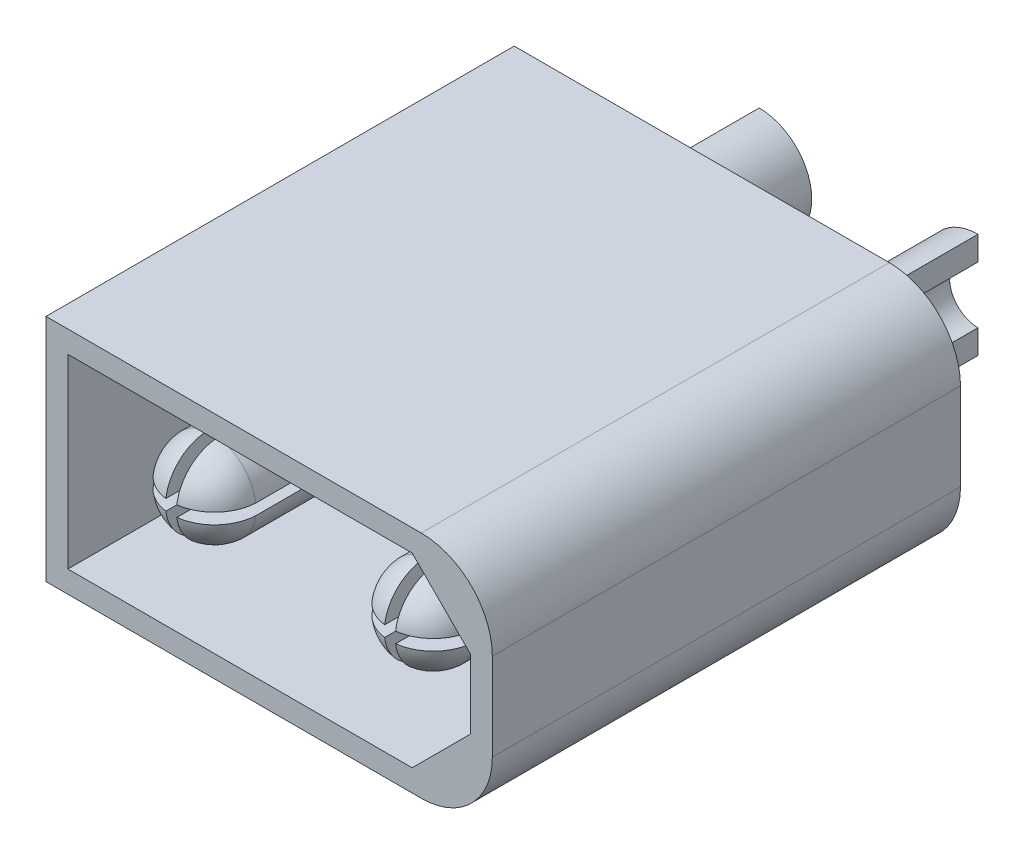
SolidWorks part; units mm, degrees
ref_plane "Front Plane" through (0, 0, 0) normal (0, 0, 1) x (1, 0, 0)
ref_plane "Top Plane" through (0, 0, 0) normal (0, 1, 0) x (1, 0, 0)
ref_plane "Right Plane" through (0, 0, 0) normal (1, 0, 0) x (0, 0, -1)
sketch "Sketch1" plane through (0, 0, 0) normal (0, 0, 1) x (1, 0, 0)
  line L0 (0, 0) -> (10.2, 0) construction
  line L1 (0, -2.625) -> (0, 2.625)
  line L2 (0, 2.625) -> (8.575, 2.625)
  line L4 (10.2, 1) -> (10.2, -1)
  line L5 (5.1, 0) -> (5.1, 1.3562) construction
  line L7 (0, -2.625) -> (8.575, -2.625)
  line L8 (0.5, 2.125) -> (8.3679, 2.125)
  line L9 (8.3679, 2.125) -> (9.7, 0.7929)
  line L10 (9.7, 0.7929) -> (9.7, -0.7929)
  line L11 (8.3679, -2.125) -> (9.7, -0.7929)
  line L12 (0.5, -2.125) -> (8.3679, -2.125)
  line L13 (0.5, -2.125) -> (0.5, 2.125)
  line L14 (8.575, 2.625) -> (10.2, 1) construction
  line L15 (8.575, -2.625) -> (10.2, -1) construction
  circle A0 centre (2.6, 0) radius 1
  circle A2 centre (7.6, 0) radius 1
  arc A3 (8.575, 2.625) -> (10.2, 1) centre (8.575, 1) cw
  arc A4 (8.575, -2.625) -> (10.2, -1) centre (8.575, -1) ccw
  dimension "D6" = 2
  dimension "D1" = 5.25
  dimension "D2" = 10.2
  dimension "D3" = 135
  dimension "D4" = 2.5
  dimension "D7" = 2
  dimension "D5" = 0.5
extrude "Boss-Extrude1" add sketch "Sketch1" along normal blind 10.7 contours L1 L7 A4 L4 A3 L2 L12 L13 L8 L9 L10 L11 region at (0.1147, 0, 0)
extrude "Boss-Extrude5" add sketch "Sketch1<4>" along normal blind 9.5 separate body contours A0 | A2 region at (2.6, 0, 0)
sketch "Sketch1<4>" plane through (0, 0, 0) normal (0, 0, 1) x (1, 0, 0) same geometry as "Sketch1"
ref_plane "Plane1" through (0, 0, 1) normal (0, 0, -1) x (-1, 0, 0)
sketch "Sketch3" plane through (0, 0, 1) normal (0, 0, -1) x (-1, 0, 0)
  line L0 (-0.5, -2.125) -> (-0.5, 2.125) construction
  line L1 (-0.5, -2.125) -> (-8.3679, -2.125) construction
  line L2 (-8.3679, -2.125) -> (-9.7, -0.7929) construction
  line L3 (-9.7, 0.7929) -> (-9.7, -0.7929) construction
  line L4 (-8.3679, 2.125) -> (-9.7, 0.7929) construction
  line L5 (-0.5, 2.125) -> (-8.3679, 2.125) construction
  line L6 (-0.5, -2.125) -> (-0.5, 2.125)
  line L7 (-0.5, -2.125) -> (-8.3679, -2.125)
  line L8 (-8.3679, -2.125) -> (-9.7, -0.7929)
  line L9 (-9.7, 0.7929) -> (-9.7, -0.7929)
  line L10 (-8.3679, 2.125) -> (-9.7, 0.7929)
  line L11 (-0.5, 2.125) -> (-8.3679, 2.125)
extrude "Boss-Extrude3" add sketch "Sketch3" against normal blind 2.5
dome "Dome1" faces to dome 1 distance 0.95 reverse direction no elliptical dome no face at (6.6, 0, 9.5) parameters "D1"=0.95
dome "Dome2" faces to dome 1 distance 0.95 reverse direction no elliptical dome no face at (3.6, 0, 9.5) parameters "D1"=0.95
ref_plane "Plane2" through (0, 0, 6) normal (0, 0, 1) x (1, 0, 0)
sketch "Sketch4" plane through (0, 0, 6) normal (0, 0, 1) x (1, 0, 0)
  line L0 (7.6, 0) -> (2.6, 0) construction
  line L1 (5.1, 0) -> (5.1, -4.8964) construction
  line L2 (7.6, 0) -> (7.6, 1) construction
  line L3 (7.475, 0.9922) -> (7.475, 0.125)
  line L4 (7.725, 0.9922) -> (7.725, 0.125)
  line L5 (8.5922, -0.125) -> (7.725, -0.125)
  line L6 (8.5922, 0.125) -> (7.725, 0.125)
  line L7 (7.475, -0.9922) -> (7.475, -0.125)
  line L8 (7.725, -0.9922) -> (7.725, -0.125)
  line L9 (6.6078, 0.125) -> (7.475, 0.125)
  line L10 (6.6078, -0.125) -> (7.475, -0.125)
  line L11 (2.6, 0) -> (2.6, 1) construction
  line L12 (3.5922, -0.125) -> (2.725, -0.125)
  line L13 (3.5922, 0.125) -> (2.725, 0.125)
  line L14 (2.475, -0.9922) -> (2.475, -0.125)
  line L15 (2.725, -0.9922) -> (2.725, -0.125)
  line L16 (1.6078, 0.125) -> (2.475, 0.125)
  line L17 (1.6078, -0.125) -> (2.475, -0.125)
  line L18 (2.475, 0.9922) -> (2.475, 0.125)
  line L19 (2.725, 0.9922) -> (2.725, 0.125)
  circle A0 centre (7.6, 0) radius 1 construction
  circle A1 centre (2.6, 0) radius 1 construction
  arc A2 (7.725, 0.9922) -> (7.475, 0.9922) centre (7.6, 0) ccw
  circle A3 centre (2.6, 0) radius 1 construction
  arc A4 (8.5922, -0.125) -> (8.5922, 0.125) centre (7.6, 0) ccw
  arc A5 (7.475, -0.9922) -> (7.725, -0.9922) centre (7.6, 0) ccw
  arc A6 (6.6078, 0.125) -> (6.6078, -0.125) centre (7.6, 0) ccw
  arc A7 (3.5922, 0.125) -> (3.5922, -0.125) centre (2.6, 0) cw
  arc A8 (2.725, -0.9922) -> (2.475, -0.9922) centre (2.6, 0) cw
  arc A9 (1.6078, -0.125) -> (1.6078, 0.125) centre (2.6, 0) cw
  arc A10 (2.475, 0.9922) -> (2.725, 0.9922) centre (2.6, 0) cw
  point P28 (7.6, 0)
  dimension "D1" = 0.25
  dimension "D2" = 4
extrude "Cut-Extrude1" cut sketch "Sketch4" along normal through all
sketch "Sketch5" plane through (0, 0, 3.5) normal (0, 0, 1) x (1, 0, 0)
  circle A0 centre (7.6, 0) radius 1.2
  circle A1 centre (2.6, 0) radius 1.2
  dimension "D1" = 2.4
extrude "Boss-Extrude6" add sketch "Sketch5" against normal offset from surface (6.5 mm away) 3 up to face at (6.1893, 0, 0) offset beyond the face yes
sketch "Sketch6" plane through (0, 0, -3) normal (0, 0, -1) x (-1, 0, 0)
  circle A0 centre (-2.6, 0) radius 0.65
  circle A1 centre (-7.6, 0) radius 0.65
  circle A2 centre (-2.6, 0) radius 1.2 construction
  dimension "D1" = 0.55
extrude "Cut-Extrude2" cut sketch "Sketch6" against normal up to surface (4 mm away) up to face at (1.4, 0, 1)
sketch "Sketch7" plane through (0, 0, -3) normal (0, 0, -1) x (-1, 0, 0)
  line L0 (-2.6, -1.2) -> (-2.6, 1.2)
  line L1 (-7.6, -1.2) -> (-7.6, 1.2)
  circle A1 centre (-2.6, 0) radius 1.2
  circle A2 centre (-2.6, 0) radius 1.2
  circle A3 centre (-7.6, 0) radius 1.2
  circle A4 centre (-7.6, 0) radius 1.2
  circle M3 centre (-2.6, 0) radius 0.65
  circle M4 centre (-2.6, 0) radius 1.2
  dimension "D1" = 0
  dimension "D2" = 0
extrude "Cut-Extrude3" cut sketch "Sketch7" against normal blind 2.34 contours L0 M4 M3 | L1 A4 region at (2.5732, -0.925, -3) region at (8.1093, 0, -3)
